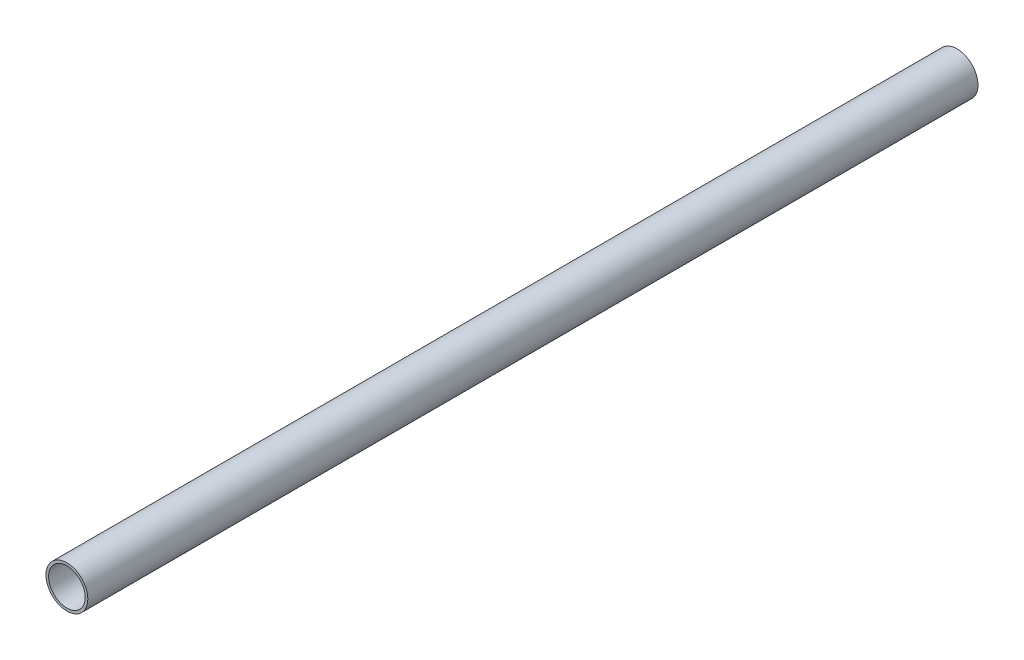
SolidWorks part; units mm, degrees
material "PC High Viscosity"
ref_plane "Front Plane" through (0, 0, 0) normal (0, 0, 1) x (1, 0, 0)
ref_plane "Top Plane" through (0, 0, 0) normal (0, 1, 0) x (1, 0, 0)
ref_plane "Right Plane" through (0, 0, 0) normal (1, 0, 0) x (0, 0, -1)
sketch "Sketch2" plane through (0, 0, 0) normal (0, 0, 1) x (1, 0, 0)
  circle A0 centre (0, 0) radius 11.1125
  circle A1 centre (0, 0) radius 12.7
  dimension "D1" = 25.4
  dimension "D2" = 22.225
extrude "Boss-Extrude1" add sketch "Sketch2" along normal mid plane 540.2
equation "\"D1@Boss-Extrude1\"=21.125in+3.625mm"
